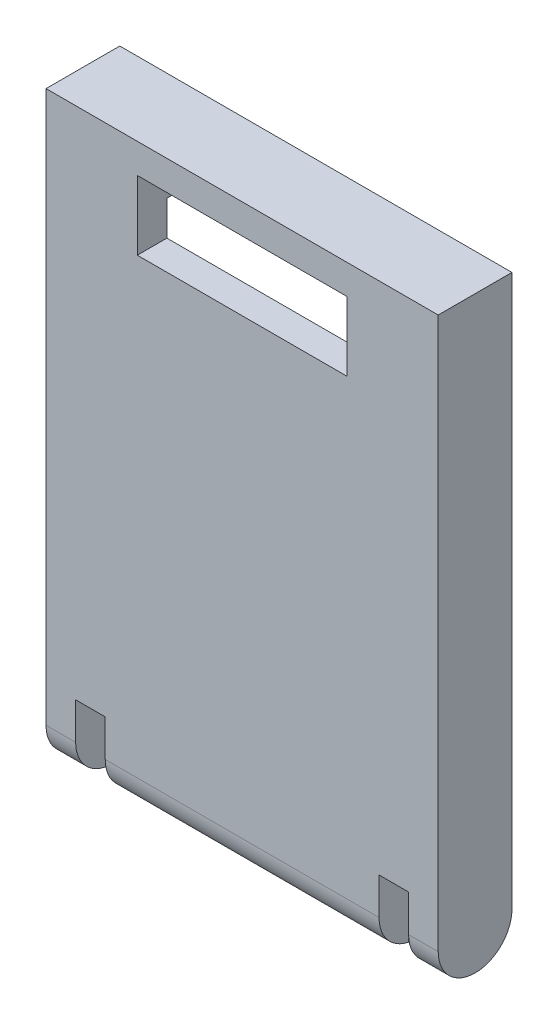
SolidWorks part; units mm, degrees
ref_plane "Front Plane" through (0, 0, 0) normal (0, 0, 1) x (1, 0, 0)
ref_plane "Top Plane" through (0, 0, 0) normal (0, 1, 0) x (1, 0, 0)
ref_plane "Right Plane" through (0, 0, 0) normal (1, 0, 0) x (0, 0, -1)
sketch "Sketch2" plane through (0, 0, 0) normal (1, 0, 0) x (0, 0, -1)
  line L0 (-1.495, 0) -> (1.495, 0)
  line L1 (1.495, 0) -> (1.495, -22.355)
  line L3 (-1.495, -22.355) -> (-1.495, 0)
  line L4 (-1.495, -22.355) -> (1.495, -22.355) construction
  arc A0 (-1.495, -22.355) -> (1.495, -22.355) centre (0, -22.355) ccw
  point P5 (0, -23.85)
  point P6 (0, 0)
  dimension "D1" = 23.85
  dimension "D2" = 2.99
extrude "Boss-Extrude1" add sketch "Sketch2" against normal blind 15.9
shell "Shell1" thickness 1.2 removed face at (-7.95, -11.1775, -1.495)
sketch "Sketch3" plane through (0, 0, 1.495) normal (0, 0, 1) x (1, 0, 0)
  line L2 (-12.2, -4) -> (-3.7, -4)
  line L3 (-3.7, -4) -> (-3.7, -1.2)
  line L4 (-3.7, -1.2) -> (-12.2, -1.2)
  line L5 (-12.2, -1.2) -> (-12.2, -4)
  line L6 (-7.95, 0) -> (-7.95, -2.4) construction
  line L7 (-15.9, 0) -> (0, 0) construction
  point P8 (-7.95, -1.2)
  dimension "D1" = 8.5
  dimension "D2" = 1.2
  dimension "D3" = 2.8
extrude "Cut-Extrude1" cut sketch "Sketch3" against normal through all both and the other way through all
ref_plane "Plane1" through (-14.7, 0, 0) normal (-1, 0, 0) x (0, 0, 1)
sketch "Sketch4" plane through (-14.7, 0, 0) normal (-1, 0, 0) x (0, 0, 1)
  line L3 (1.495, -20.86) -> (-1.495, -20.86)
  line L6 (1.495, -22.355) -> (1.495, 0)
  line L7 (-1.495, 0) -> (-1.495, -22.355)
  line L8 (1.495, 0) -> (-1.495, 0)
  line L9 (1.495, -22.355) -> (1.495, -20.86)
  line L10 (-1.495, -20.86) -> (-1.495, -22.355)
  circle A1 centre (0, -22.355) radius 1.495 construction
  arc A2 (-1.495, -22.355) -> (1.495, -22.355) centre (0, -22.355) ccw
  arc A3 (-1.495, -22.355) -> (1.495, -22.355) centre (0, -22.355) ccw
  dimension "D1" = 0
extrude "Cut-Extrude2" cut sketch "Sketch4" against normal blind 1.2
pattern_linear "LPattern1" count 2 spacing 12.3 along (1, 0, 0) of "Cut-Extrude2"
ref_plane "Plane2" through (0, 0, -1.495) normal (0, 0, -1) x (-1, 0, 0)
sketch "Sketch5" plane through (0, 0, -1.495) normal (0, 0, -1) x (-1, 0, 0)
  line L0 (2.4, -20.86) -> (13.5, -20.86)
  line L1 (13.5, -20.86) -> (13.5, -23.85)
  line L2 (13.5, -23.85) -> (2.4, -23.85)
  line L3 (2.4, -23.85) -> (2.4, -20.86)
  line L5 (13.5, -20.86) -> (14.7, -20.86) construction
  line L6 (0, -23.85) -> (1.2, -23.85) construction
  line L7 (13.5, -20.86) -> (13.5, -22.355) construction
  point P10 (13.5, -21.6075)
  dimension "D1" = 11.1
extrude "Cut-Extrude5" cut sketch "Sketch5" against normal blind 0.8
sketch "Sketch6" plane through (0, 0, 0.295) normal (0, 0, -1) x (-1, 0, 0)
  line L1 (2.4, -20.86) -> (13.5, -20.86)
  line L2 (13.5, -20.86) -> (13.5, -23.85)
  line L3 (13.5, -23.85) -> (12.3, -23.85)
  line L4 (12.3, -23.85) -> (3.6, -23.85)
  line L5 (12.3, -22.65) -> (12.3, -22.06)
  line L6 (12.3, -22.06) -> (3.6, -22.06)
  line L9 (3.6, -22.65) -> (12.3, -22.65)
  line L11 (2.4, -23.85) -> (3.6, -23.85)
  line L13 (2.4, -23.85) -> (2.4, -20.86)
  line L14 (2.4, -23.85) -> (13.5, -23.85) construction
  line L15 (3.6, -22.65) -> (3.6, -22.06)
  dimension "D1" = 1.2
  dimension "D2" = 1.2
  dimension "D3" = 1.2
  dimension "D4" = 1.2
  dimension "D5" = 1.2
  dimension "D6" = 1.2
extrude "Boss-Extrude2" add sketch "Sketch6" along normal blind 1.1
sketch "Sketch7" plane through (0, -23.85, 0) normal (0, -1, 0) x (1, 0, 0)
  line L4 (-2.4, -0.805) -> (-2.4, 0.295)
  line L5 (-2.4, 0.295) -> (-13.5, 0.295)
  line L6 (-13.5, 0.295) -> (-13.5, -0.805)
  line L7 (-13.5, -0.805) -> (-2.4, -0.805)
  line L8 (-2.4, -0.805) -> (-2.4, 0.295)
  line L9 (-2.4, 0.295) -> (-13.5, 0.295)
  line L10 (-13.5, 0.295) -> (-13.5, -0.805)
  line L11 (-13.5, -0.805) -> (-2.4, -0.805)
  dimension "D1" = 0
extrude "Cut-Extrude6" cut sketch "Sketch7" against normal blind 0.17
sketch "Sketch8" plane through (0, 0, 0.295) normal (0, 0, -1) x (-1, 0, 0)
  line L0 (3.7, -2.6) -> (3.2, -2.6)
  line L1 (3.7, -4) -> (3.7, -1.2) construction
  line L2 (3.2, -2.6) -> (3.2, -1.2)
  line L4 (3.2, -1.2) -> (3.7, -1.2)
  line L5 (3.7, -1.2) -> (3.7, -2.6)
  dimension "D1" = 0.5
extrude "Boss-Extrude3" add sketch "Sketch8" along normal blind 2.5
pattern_linear "LPattern2" count 2 spacing 9 along (-1, 0, 0) of "Boss-Extrude3"
